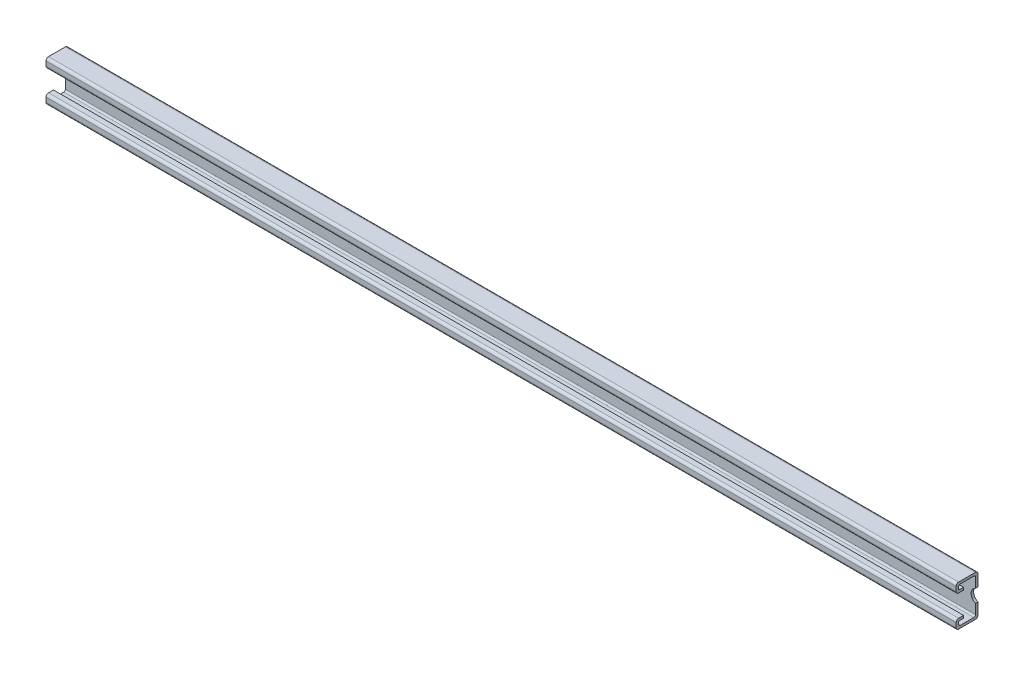
SolidWorks part; units mm, degrees
material "1023 Carbon Steel Sheet (SS)"
ref_plane "Front Plane" through (0, 0, 0) normal (0, 0, 1) x (1, 0, 0)
ref_plane "Top Plane" through (0, 0, 0) normal (0, 1, 0) x (1, 0, 0)
ref_plane "Right Plane" through (0, 0, 0) normal (1, 0, 0) x (0, 0, -1)
ref_plane "Plane1" through (0, 0, -11) normal (0, 0, -1) x (-1, 0, 0)
sketch "Sketch1" plane through (0, 0, -11) normal (0, 0, -1) x (-1, 0, 0)
  line L0 (0, 0) -> (0, 41)
  line L1 (0, 41) -> (-1000, 41)
  line L2 (-1000, 41) -> (-1000, 0)
  line L3 (-1000, 0) -> (0, 0)
extrude "Boss-Extrude1" add sketch "Sketch1" against normal blind 22
sketch "Sketch2" plane through (1000, 0, 0) normal (1, 0, 0) x (0, 0, -1)
  line L0 (-11, 9.5) -> (-3.5, 9.5)
  line L1 (-3.5, 9.5) -> (-3.5, 7)
  line L2 (-3.5, 7) -> (-8.5, 7)
  line L3 (-8.5, 7) -> (-8.5, 2.5)
  line L4 (-8.5, 2.5) -> (8.5, 2.5)
  line L5 (8.5, 2.5) -> (8.5, 38.5)
  line L6 (8.5, 38.5) -> (-8.5, 38.5)
  line L7 (-8.5, 38.5) -> (-8.5, 31.5)
  line L8 (-8.5, 31.5) -> (-11, 31.5)
  line L9 (-11, 31.5) -> (-11, 9.5)
extrude "Cut-Extrude1" cut sketch "Sketch2" against normal through all
sketch "Sketch3" plane through (0, 0, 8.5) normal (0, 0, -1) x (-1, 0, 0)
  line L0 (0, 34) -> (0, 31.5)
  line L1 (0, 31.5) -> (-1000, 31.5)
  line L2 (-1000, 31.5) -> (-1000, 34)
  line L3 (-1000, 34) -> (0, 34)
extrude "Boss-Extrude2" add sketch "Sketch3" along normal blind 5
sketch "Sketch4" plane through (0, 0, -11) normal (0, 0, -1) x (-1, 0, 0)
  line L0 (-117, 27.5) -> (-133, 27.5)
  line L1 (-133, 13.5) -> (-117, 13.5)
  arc A0 (-133, 27.5) -> (-133, 13.5) centre (-133, 20.5) ccw
  arc A1 (-117, 13.5) -> (-117, 27.5) centre (-117, 20.5) ccw
extrude "Cut-Extrude2" cut sketch "Sketch4" against normal through all
sketch "Sketch5" plane through (0, 0, -11) normal (0, 0, -1) x (-1, 0, 0)
  line L0 (-217, 27.5) -> (-233, 27.5)
  line L1 (-233, 13.5) -> (-217, 13.5)
  arc A0 (-233, 27.5) -> (-233, 13.5) centre (-233, 20.5) ccw
  arc A1 (-217, 13.5) -> (-217, 27.5) centre (-217, 20.5) ccw
extrude "Cut-Extrude3" cut sketch "Sketch5" against normal through all
sketch "Sketch6" plane through (0, 0, -11) normal (0, 0, -1) x (-1, 0, 0)
  line L0 (-317, 27.5) -> (-333, 27.5)
  line L1 (-333, 13.5) -> (-317, 13.5)
  arc A0 (-333, 27.5) -> (-333, 13.5) centre (-333, 20.5) ccw
  arc A1 (-317, 13.5) -> (-317, 27.5) centre (-317, 20.5) ccw
extrude "Cut-Extrude4" cut sketch "Sketch6" against normal through all
sketch "Sketch7" plane through (0, 0, -11) normal (0, 0, -1) x (-1, 0, 0)
  line L0 (-417, 27.5) -> (-433, 27.5)
  line L1 (-433, 13.5) -> (-417, 13.5)
  arc A0 (-433, 27.5) -> (-433, 13.5) centre (-433, 20.5) ccw
  arc A1 (-417, 13.5) -> (-417, 27.5) centre (-417, 20.5) ccw
extrude "Cut-Extrude5" cut sketch "Sketch7" against normal through all
sketch "Sketch8" plane through (0, 0, -11) normal (0, 0, -1) x (-1, 0, 0)
  line L0 (-517, 27.5) -> (-533, 27.5)
  line L1 (-533, 13.5) -> (-517, 13.5)
  arc A0 (-533, 27.5) -> (-533, 13.5) centre (-533, 20.5) ccw
  arc A1 (-517, 13.5) -> (-517, 27.5) centre (-517, 20.5) ccw
extrude "Cut-Extrude6" cut sketch "Sketch8" against normal through all
sketch "Sketch9" plane through (0, 0, -11) normal (0, 0, -1) x (-1, 0, 0)
  line L0 (-617, 27.5) -> (-633, 27.5)
  line L1 (-633, 13.5) -> (-617, 13.5)
  arc A0 (-633, 27.5) -> (-633, 13.5) centre (-633, 20.5) ccw
  arc A1 (-617, 13.5) -> (-617, 27.5) centre (-617, 20.5) ccw
extrude "Cut-Extrude7" cut sketch "Sketch9" against normal through all
sketch "Sketch10" plane through (0, 0, -11) normal (0, 0, -1) x (-1, 0, 0)
  line L0 (-717, 27.5) -> (-733, 27.5)
  line L1 (-733, 13.5) -> (-717, 13.5)
  arc A0 (-733, 27.5) -> (-733, 13.5) centre (-733, 20.5) ccw
  arc A1 (-717, 13.5) -> (-717, 27.5) centre (-717, 20.5) ccw
extrude "Cut-Extrude8" cut sketch "Sketch10" against normal through all
sketch "Sketch11" plane through (0, 0, -11) normal (0, 0, -1) x (-1, 0, 0)
  line L0 (-817, 27.5) -> (-833, 27.5)
  line L1 (-833, 13.5) -> (-817, 13.5)
  arc A0 (-833, 27.5) -> (-833, 13.5) centre (-833, 20.5) ccw
  arc A1 (-817, 13.5) -> (-817, 27.5) centre (-817, 20.5) ccw
extrude "Cut-Extrude9" cut sketch "Sketch11" against normal through all
sketch "Sketch12" plane through (0, 0, -11) normal (0, 0, -1) x (-1, 0, 0)
  line L0 (-917, 27.5) -> (-933, 27.5)
  line L1 (-933, 13.5) -> (-917, 13.5)
  arc A0 (-933, 27.5) -> (-933, 13.5) centre (-933, 20.5) ccw
  arc A1 (-917, 13.5) -> (-917, 27.5) centre (-917, 20.5) ccw
extrude "Cut-Extrude10" cut sketch "Sketch12" against normal through all
sketch "Sketch13" plane through (0, 0, -11) normal (0, 0, -1) x (-1, 0, 0)
  line L0 (-17, 27.5) -> (-33, 27.5)
  line L1 (-33, 13.5) -> (-17, 13.5)
  arc A0 (-33, 27.5) -> (-33, 13.5) centre (-33, 20.5) ccw
  arc A1 (-17, 13.5) -> (-17, 27.5) centre (-17, 20.5) ccw
extrude "Cut-Extrude11" cut sketch "Sketch13" against normal through all
sketch "Sketch14" plane through (0, 0, -11) normal (0, 0, -1) x (-1, 0, 0)
  line L0 (-967, 27.5) -> (-983, 27.5)
  line L1 (-983, 13.5) -> (-967, 13.5)
  arc A0 (-983, 27.5) -> (-983, 13.5) centre (-983, 20.5) ccw
  arc A1 (-967, 13.5) -> (-967, 27.5) centre (-967, 20.5) ccw
extrude "Cut-Extrude12" cut sketch "Sketch14" against normal through all
sketch "Sketch15" plane through (0, 0, -11) normal (0, 0, -1) x (-1, 0, 0)
  line L0 (-867, 27.5) -> (-883, 27.5)
  line L1 (-883, 13.5) -> (-867, 13.5)
  arc A0 (-883, 27.5) -> (-883, 13.5) centre (-883, 20.5) ccw
  arc A1 (-867, 13.5) -> (-867, 27.5) centre (-867, 20.5) ccw
extrude "Cut-Extrude13" cut sketch "Sketch15" against normal through all
sketch "Sketch16" plane through (0, 0, -11) normal (0, 0, -1) x (-1, 0, 0)
  line L0 (-767, 27.5) -> (-783, 27.5)
  line L1 (-783, 13.5) -> (-767, 13.5)
  arc A0 (-783, 27.5) -> (-783, 13.5) centre (-783, 20.5) ccw
  arc A1 (-767, 13.5) -> (-767, 27.5) centre (-767, 20.5) ccw
extrude "Cut-Extrude14" cut sketch "Sketch16" against normal through all
sketch "Sketch17" plane through (0, 0, -11) normal (0, 0, -1) x (-1, 0, 0)
  line L0 (-667, 27.5) -> (-683, 27.5)
  line L1 (-683, 13.5) -> (-667, 13.5)
  arc A0 (-683, 27.5) -> (-683, 13.5) centre (-683, 20.5) ccw
  arc A1 (-667, 13.5) -> (-667, 27.5) centre (-667, 20.5) ccw
extrude "Cut-Extrude15" cut sketch "Sketch17" against normal through all
sketch "Sketch18" plane through (0, 0, -11) normal (0, 0, -1) x (-1, 0, 0)
  line L0 (-567, 27.5) -> (-583, 27.5)
  line L1 (-583, 13.5) -> (-567, 13.5)
  arc A0 (-583, 27.5) -> (-583, 13.5) centre (-583, 20.5) ccw
  arc A1 (-567, 13.5) -> (-567, 27.5) centre (-567, 20.5) ccw
extrude "Cut-Extrude16" cut sketch "Sketch18" against normal through all
sketch "Sketch19" plane through (0, 0, -11) normal (0, 0, -1) x (-1, 0, 0)
  line L0 (-467, 27.5) -> (-483, 27.5)
  line L1 (-483, 13.5) -> (-467, 13.5)
  arc A0 (-483, 27.5) -> (-483, 13.5) centre (-483, 20.5) ccw
  arc A1 (-467, 13.5) -> (-467, 27.5) centre (-467, 20.5) ccw
extrude "Cut-Extrude17" cut sketch "Sketch19" against normal through all
sketch "Sketch20" plane through (0, 0, -11) normal (0, 0, -1) x (-1, 0, 0)
  line L0 (-367, 27.5) -> (-383, 27.5)
  line L1 (-383, 13.5) -> (-367, 13.5)
  arc A0 (-383, 27.5) -> (-383, 13.5) centre (-383, 20.5) ccw
  arc A1 (-367, 13.5) -> (-367, 27.5) centre (-367, 20.5) ccw
extrude "Cut-Extrude18" cut sketch "Sketch20" against normal through all
sketch "Sketch21" plane through (0, 0, -11) normal (0, 0, -1) x (-1, 0, 0)
  line L0 (-267, 27.5) -> (-283, 27.5)
  line L1 (-283, 13.5) -> (-267, 13.5)
  arc A0 (-283, 27.5) -> (-283, 13.5) centre (-283, 20.5) ccw
  arc A1 (-267, 13.5) -> (-267, 27.5) centre (-267, 20.5) ccw
extrude "Cut-Extrude19" cut sketch "Sketch21" against normal through all
sketch "Sketch22" plane through (0, 0, -11) normal (0, 0, -1) x (-1, 0, 0)
  line L0 (-167, 27.5) -> (-183, 27.5)
  line L1 (-183, 13.5) -> (-167, 13.5)
  arc A0 (-183, 27.5) -> (-183, 13.5) centre (-183, 20.5) ccw
  arc A1 (-167, 13.5) -> (-167, 27.5) centre (-167, 20.5) ccw
extrude "Cut-Extrude20" cut sketch "Sketch22" against normal through all
sketch "Sketch23" plane through (0, 0, -11) normal (0, 0, -1) x (-1, 0, 0)
  line L0 (-67, 27.5) -> (-83, 27.5)
  line L1 (-83, 13.5) -> (-67, 13.5)
  arc A0 (-83, 27.5) -> (-83, 13.5) centre (-83, 20.5) ccw
  arc A1 (-67, 13.5) -> (-67, 27.5) centre (-67, 20.5) ccw
extrude "Cut-Extrude21" cut sketch "Sketch23" against normal through all
fillet "Fillet1" radius 1.2 2 edges at (500, 7, 8.5) (500, 34, 8.5) tangent propagation no
fillet "Fillet2" radius 1.6 4 edges at (500, 2.5, -8.5) (500, 38.5, 8.5) (500, 38.5, -8.5) (500, 2.5, 8.5) tangent propagation no
fillet "Fillet3" radius 2.5 6 edges at (500, 0, -11) (500, 31.5, 11) (500, 9.5, 11) (500, 41, 11) (500, 41, -11) (500, 0, 11) tangent propagation no
sketch "Sketch24" plane through (0, 41, 0) normal (0, 1, 0) x (1, 0, 0)
  line L0 (1000, -11) -> (0, -11) construction
  line L1 (1000, 11) -> (914.4, 11)
  line L2 (1000, 11) -> (1000, -11)
  line L3 (1000, -11) -> (914.4, -11)
  line L4 (914.4, 11) -> (914.4, -11)
  line L5 (0, -8.5) -> (0, 8.5) construction
  dimension "D1" = 914.4
extrude "Cut-Extrude22" cut sketch "Sketch24" against normal through all
